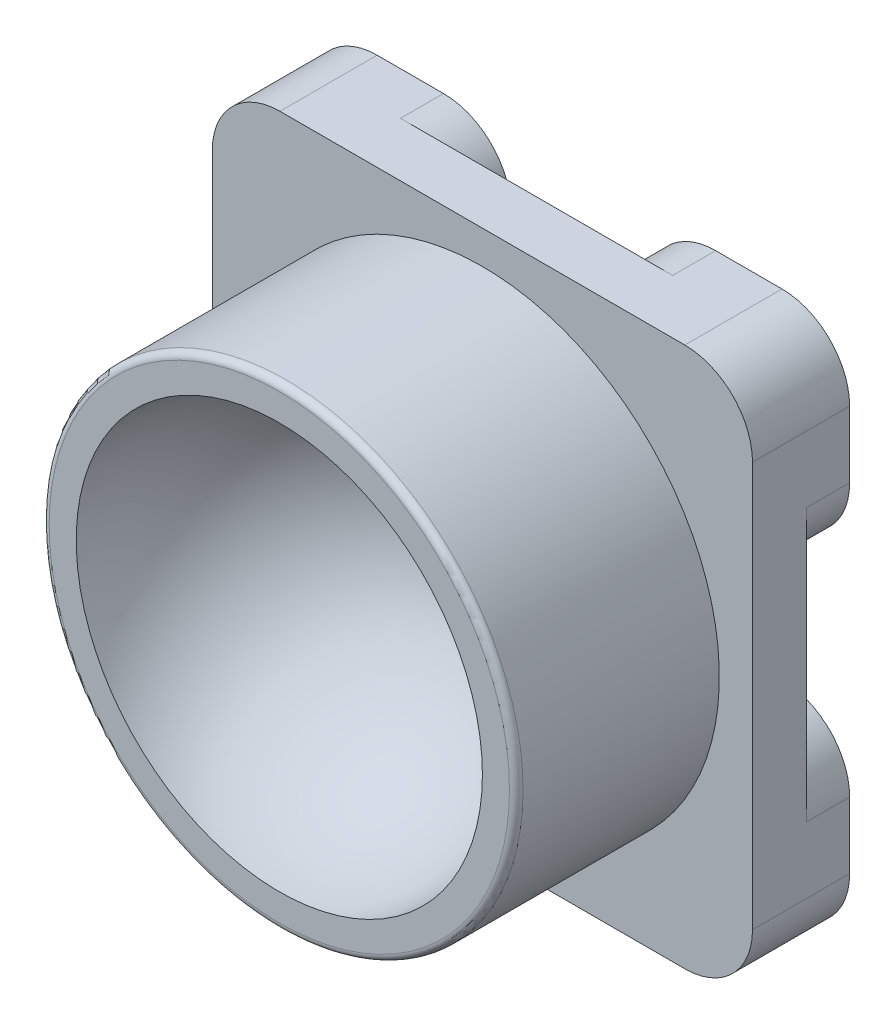
SolidWorks part; units mm, degrees
ref_plane "Front Plane" through (0, 0, 0) normal (0, 0, 1) x (1, 0, 0)
ref_plane "Top Plane" through (0, 0, 0) normal (0, 1, 0) x (1, 0, 0)
ref_plane "Right Plane" through (0, 0, 0) normal (1, 0, 0) x (0, 0, -1)
sketch "Sketch1" plane through (0, 0, 0) normal (0, 0, 1) x (1, 0, 0)
  line L5 (-14.9, 14.9) -> (14.9, 14.9)
  line L6 (-15, -15) -> (15, -15)
  line L18 (-15, -15) -> (-15, 15)
  line L19 (-15, 15) -> (15, 15)
  line L24 (15, -15) -> (15, 15)
  line L25 (-15, -15) -> (15, 15) construction
  line L26 (-15, 15) -> (15, -15) construction
  line L27 (14.9, -14.9) -> (14.9, 14.9)
  line L28 (-14.9, -14.9) -> (14.9, -14.9)
  line L29 (-14.9, -14.9) -> (-14.9, 14.9)
  line L30 (35.1, 14.9) -> (64.9, 14.9)
  line L31 (64.9, -14.9) -> (64.9, 14.9)
  line L32 (35.1, -14.9) -> (64.9, -14.9)
  line L33 (35.1, -14.9) -> (35.1, 14.9)
  line L34 (35.1, 64.9) -> (64.9, 64.9)
  line L35 (64.9, 35.1) -> (64.9, 64.9)
  line L36 (35.1, 35.1) -> (64.9, 35.1)
  line L37 (35.1, 35.1) -> (35.1, 64.9)
  line L38 (-14.9, 64.9) -> (14.9, 64.9)
  line L39 (14.9, 35.1) -> (14.9, 64.9)
  line L40 (-14.9, 35.1) -> (14.9, 35.1)
  line L41 (-14.9, 35.1) -> (-14.9, 64.9)
  line L42 (-14.9, 14.9) -> (35.1, 14.9) construction
  line L43 (-14.9, 14.9) -> (-14.9, 64.9) construction
  point P0 (0, 0)
  dimension "D1" = 30
  dimension "D2" = 30
  dimension "D5" = 2
  dimension "D6" = 50
  dimension "D7" = 50
  dimension "D3" = 0.1
  dimension "D4" = 2
extrude "Boss-Extrude1" add sketch "Sketch1" along normal blind 6.35 contours L29 L28 L27 L5 | L33 L32 L31 L30 | L37 L36 L35 L34 | L41 L40 L39 L38 region at (0, 0, 0) region at (50, 0, 0) region at (50, 50, 0) region at (0, 50, 0)
sketch "Sketch2" plane through (0, 0, 6.35) normal (0, 0, 1) x (1, 0, 0)
  line L1 (-14.9, -14.9) -> (64.9, -14.9)
  line L2 (-14.9, -14.9) -> (-14.9, 64.9)
  line L3 (-14.9, 64.9) -> (64.9, 64.9)
  line L4 (64.9, -14.9) -> (64.9, 64.9)
extrude "Boss-Extrude2" add sketch "Sketch2" along normal blind 8
fillet "Fillet2" radius 10 16 edges at (64.9, 14.9, 3.175) (64.9, -14.9, 7.175) (14.9, 14.9, 3.175) (14.9, 35.1, 3.175) (14.9, -14.9, 3.175) (-14.9, -14.9, 7.175) (-14.9, 14.9, 3.175) (-14.9, 35.1, 3.175) (-14.9, 64.9, 7.175) (14.9, 64.9, 3.175) (35.1, -14.9, 3.175) (35.1, 14.9, 3.175) (35.1, 35.1, 3.175) (35.1, 64.9, 3.175) (64.9, 64.9, 7.175) (64.9, 35.1, 3.175)
sketch "Sketch3" plane through (0, 0, 14.35) normal (0, 0, 1) x (1, 0, 0)
  line L0 (25, 64.9) -> (25, -14.9) construction
  line L1 (54.9, 64.9) -> (-4.9, 64.9) construction
  line L2 (-4.9, -14.9) -> (54.9, -14.9) construction
  line L3 (-14.9, 25) -> (64.9, 25) construction
  line L4 (-14.9, 54.9) -> (-14.9, -4.9) construction
  line L5 (64.9, -4.9) -> (64.9, 54.9) construction
  circle A0 centre (25, 25) radius 30
  circle A1 centre (25, 25) radius 35
  point P15 (25, 25)
  dimension "D1" = 60
  dimension "D2" = 70
extrude "Boss-Extrude3" add sketch "Sketch3" along normal blind 30
fillet "Fillet3" radius 30 1 edges at (55, 25, 14.35) first distance on face at (55, 25, 44.35)
fillet "Fillet4" radius 1 1 edges at (60, 25, 44.35)
sketch "Sketch4" plane through (0, 0, 0) normal (0, 0, -1) x (-1, 0, 0)
  circle A0 centre (0, 50) radius 2.125
  circle A1 centre (0, 0) radius 2.125
  circle A2 centre (-50, 0) radius 2.125
  circle A3 centre (-50, 50) radius 2.125
  dimension "D1" = 4.25
extrude "Cut-Extrude1" cut sketch "Sketch4" against normal blind 5
sketch "Sketch6" plane through (0, 0, 44.35) normal (0, 0, 1) x (1, 0, 0)
  circle A0 centre (25, 25) radius 5
  dimension "D1" = 10
extrude "Cut-Extrude2" cut sketch "Sketch6" against normal up to surface (30 mm away) up to face at (-10, 25, 14.35)
sketch "Sketch7" plane through (0, 0, 6.35) normal (0, 0, -1) x (-1, 0, 0)
  circle A0 centre (-25, 25) radius 1.75
  dimension "D1" = 3.5
extrude "Cut-Extrude3" cut sketch "Sketch7" against normal through all
sketch "Sketch8" plane through (0, 0, 6.35) normal (0, 0, -1) x (-1, 0, 0)
  circle A0 centre (-25, 25) radius 3
  dimension "D1" = 6
extrude "Cut-Extrude4" cut sketch "Sketch8" against normal blind 4
